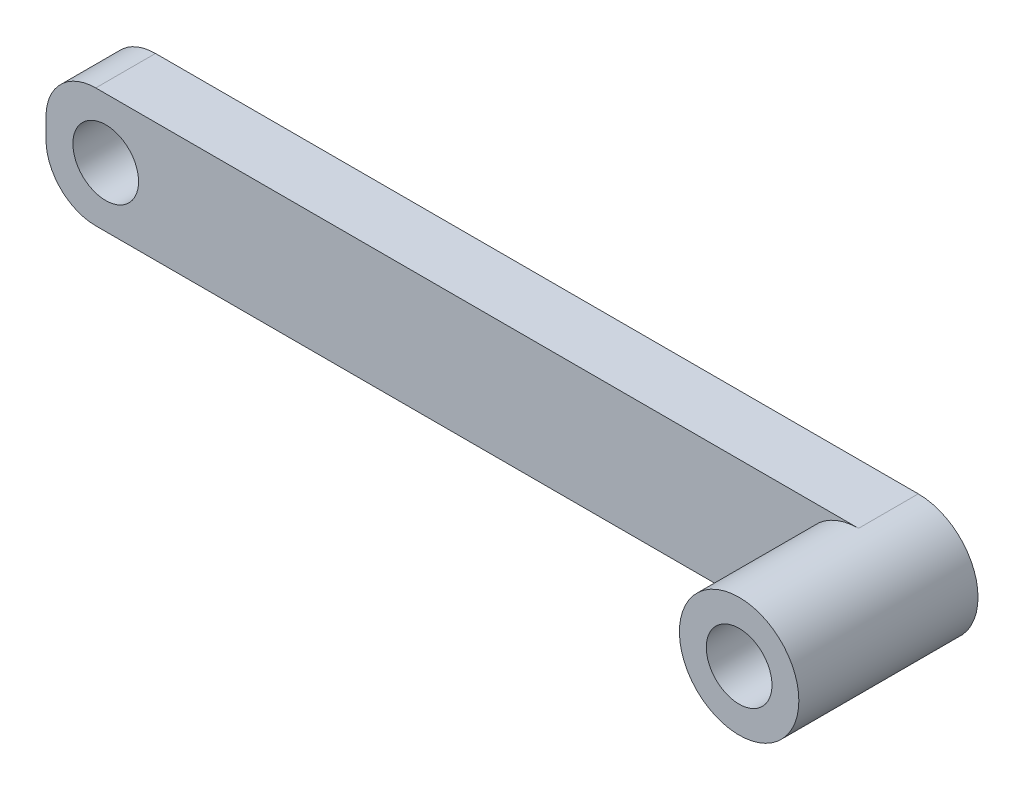
SolidWorks part; units mm, degrees
ref_plane "Front Plane" through (0, 0, 0) normal (0, 0, 1) x (1, 0, 0)
ref_plane "Top Plane" through (0, 0, 0) normal (0, 1, 0) x (1, 0, 0)
ref_plane "Right Plane" through (0, 0, 0) normal (1, 0, 0) x (0, 0, -1)
sketch "Sketch1" plane through (0, 0, 0) normal (0, 0, 1) x (1, 0, 0)
  line L0 (-18.91, 3) -> (-21.91, 3)
  line L1 (-18.91, 3) -> (18.91, 3)
  line L2 (-18.91, 3) -> (-18.91, -3)
  line L3 (-18.91, -3) -> (18.91, -3)
  line L4 (18.91, 3) -> (18.91, -3)
  line L5 (-18.91, 3) -> (18.91, -3) construction
  line L6 (-18.91, -3) -> (18.91, 3) construction
  line L7 (-21.91, 3) -> (-21.91, -3)
  line L8 (-21.91, -3) -> (-18.91, -3)
  line L10 (22.4534, -3) -> (18.91, -3)
  line L11 (18.91, 3) -> (22.4534, 3)
  line L12 (22.4534, 3) -> (22.4534, -3)
  circle A0 centre (-18.91, 0) radius 1.65
  circle A1 centre (18.91, 0) radius 1.65
  circle A2 centre (18.91, 0) radius 3
  point P0 (0, 0)
  dimension "D3" = 3.3
  dimension "D5" = 6
  dimension "D1" = 37.82
  dimension "D2" = 6
  dimension "D4" = 3
extrude "Boss-Extrude1" add sketch "Sketch1" along normal blind 3 contours A2 L1 L2 A0 L3 | A0 L2 L0 L7 L8 region at (-20.6592, 0, 0) region at (-0.8223, 0, 0)
extrude "Boss-Extrude2" add sketch "Sketch1<3>" along normal blind 9 contours L4 A2 A1 | L4 A2 A1 region at (20.9839, 2.0739, 0) region at (18.8429, 2.325, 0)
sketch "Sketch1<3>" plane through (0, 0, 0) normal (0, 0, 1) x (1, 0, 0) same geometry as "Sketch1"
fillet "Fillet1" radius 2.5 2 edges at (-21.91, -3, 1.5) (-21.91, 3, 1.5)
